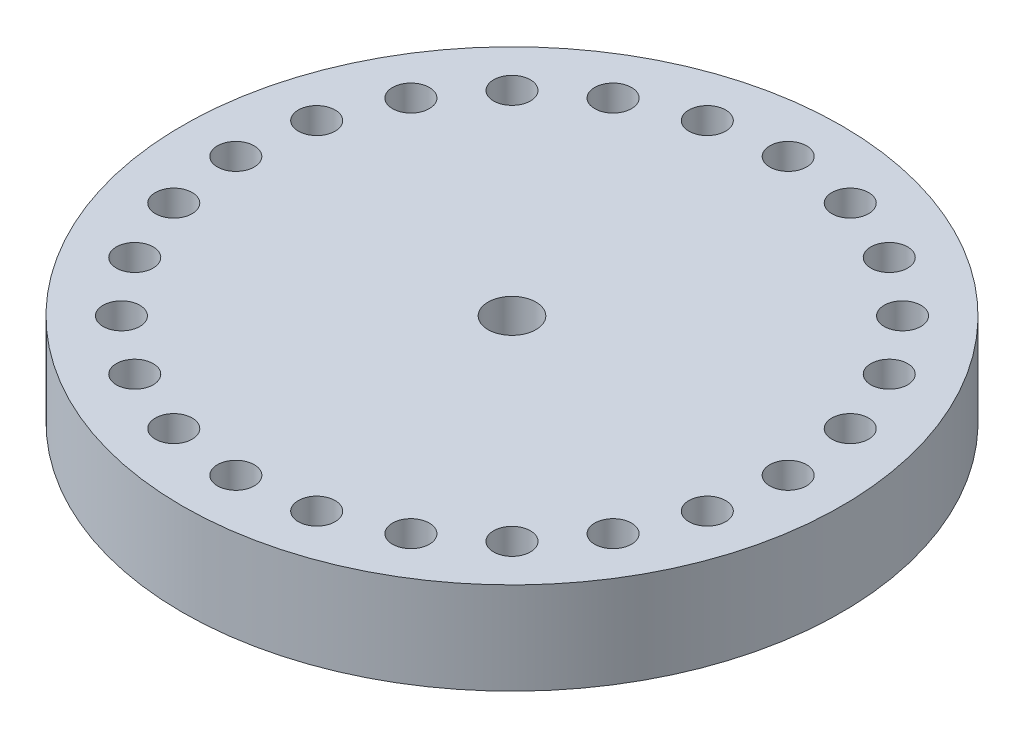
SolidWorks part; units mm, degrees
ref_plane "Front Plane" through (0, 0, 0) normal (0, 0, 1) x (1, 0, 0)
ref_plane "Top Plane" through (0, 0, 0) normal (0, 1, 0) x (1, 0, 0)
ref_plane "Right Plane" through (0, 0, 0) normal (1, 0, 0) x (0, 0, -1)
sketch "Sketch1" plane through (0, 0, 0) normal (0, 1, 0) x (1, 0, 0)
  circle A0 centre (0, 0) radius 20.066 construction
  circle A1 centre (0, 0) radius 45.466
  dimension "D1" = 25.4
extrude "Boss-Extrude1" add sketch "Sketch1" along normal blind 25.4
sketch "Sketch3" plane through (0, 0, 0) normal (0, -1, 0) x (1, 0, 0)
  circle A0 centre (0, 0) radius 20.32
extrude "Cut-Extrude1" cut sketch "Sketch3" against normal blind 12.7
sketch "Sketch4" plane through (0, 0, 0) normal (0, -1, 0) x (1, 0, 0)
  line L0 (0, 0) -> (0, 38.1) construction
  circle A0 centre (0, 38.1) radius 1.778
  dimension "D1" = 38.1
hole_wizard "CSK for 1/4 Flat Head Machine Screw1" positions "Sketch6" profile "Sketch7" countersink size "1/4" standard "ANSI Inch"
sketch "Sketch6" plane through (0, 25.4, 0) normal (0, 1, 0) x (1, 0, 0)
  point P0 (0, 0)
sketch "Sketch7" plane through (0, 25.4, 0) normal (1, 0, 0) x (0, 0, 1)
  line L0 (0, 0) -> (0, 27.3611)
  line L1 (0, 27.3611) -> (3.2639, 25.4)
  line L2 (3.2639, 25.4) -> (3.2639, 3.6524)
  line L3 (3.2639, 3.6524) -> (6.4389, 0)
  line L5 (6.4389, 0) -> (0, 0)
  line L6 (-3.2639, 3.6524) -> (-6.4389, 0) construction
  line L10 (0, 27.3611) -> (-3.2639, 25.4) construction
  line L11 (0, -6.35) -> (0, 107.95) construction
  dimension "Hole Dia." = 6.5278
  dimension "Hole Depth" = 25.4
  dimension "Near C'Sink Dia." = 12.8778
  dimension "Near C'Sink Angle" = 82
  dimension "Drill Angle" = 118
sketch "Sketch8" plane through (0, 25.4, 0) normal (0, 1, 0) x (1, 0, 0)
  circle A0 centre (0, 0) radius 46.9556
extrude "Cut-Extrude2" cut sketch "Sketch8" against normal blind 12.7
extrude "Cut-Extrude3" cut sketch "Sketch4" against normal through all
sketch "Sketch9" plane through (0, 12.7, 0) normal (0, 1, 0) x (1, 0, 0)
  circle A0 centre (0, -38.1) radius 2.54
extrude "Cut-Extrude4" cut sketch "Sketch9" against normal blind 5.08
pattern_circular "CirPattern1" count 24 every 15 about axis through (0, 12.7, 0) along (0, -1, 0) of "Cut-Extrude3", "Cut-Extrude4"
sketch "Sketch10" plane through (0, 12.7, 0) normal (0, 1, 0) x (1, 0, 0)
  circle A0 centre (0, 0) radius 22.8348
extrude "Boss-Extrude2" add sketch "Sketch10" against normal blind 5.08
sketch "Sketch11" plane through (0, 12.7, 0) normal (0, 1, 0) x (1, 0, 0)
  circle A0 centre (0, 0) radius 3.302
  dimension "D1" = 6.604
extrude "Cut-Extrude5" cut sketch "Sketch11" against normal through all
